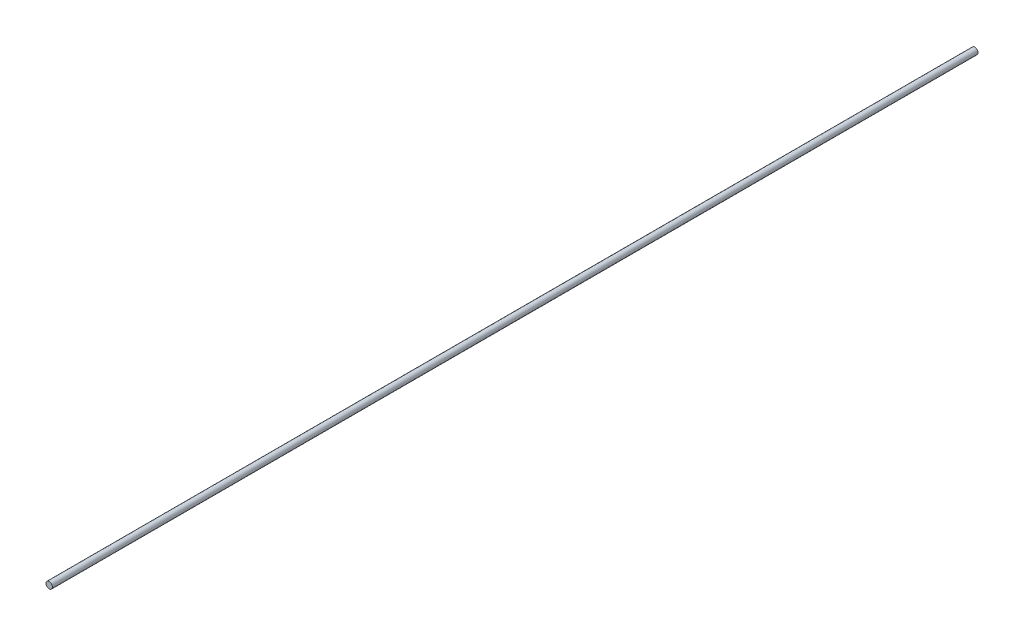
SolidWorks part; units mm, degrees
ref_plane "Front Plane" through (0, 0, 0) normal (0, 0, 1) x (1, 0, 0)
ref_plane "Top Plane" through (0, 0, 0) normal (0, 1, 0) x (1, 0, 0)
ref_plane "Right Plane" through (0, 0, 0) normal (1, 0, 0) x (0, 0, -1)
sketch "Sketch1" plane through (0, 0, 0) normal (0, 0, 1) x (1, 0, 0)
  circle A0 centre (0, 0) radius 3.175
  dimension "D1" = 6.35
extrude "Boss-Extrude1" add sketch "Sketch1" along normal mid plane 914.4
